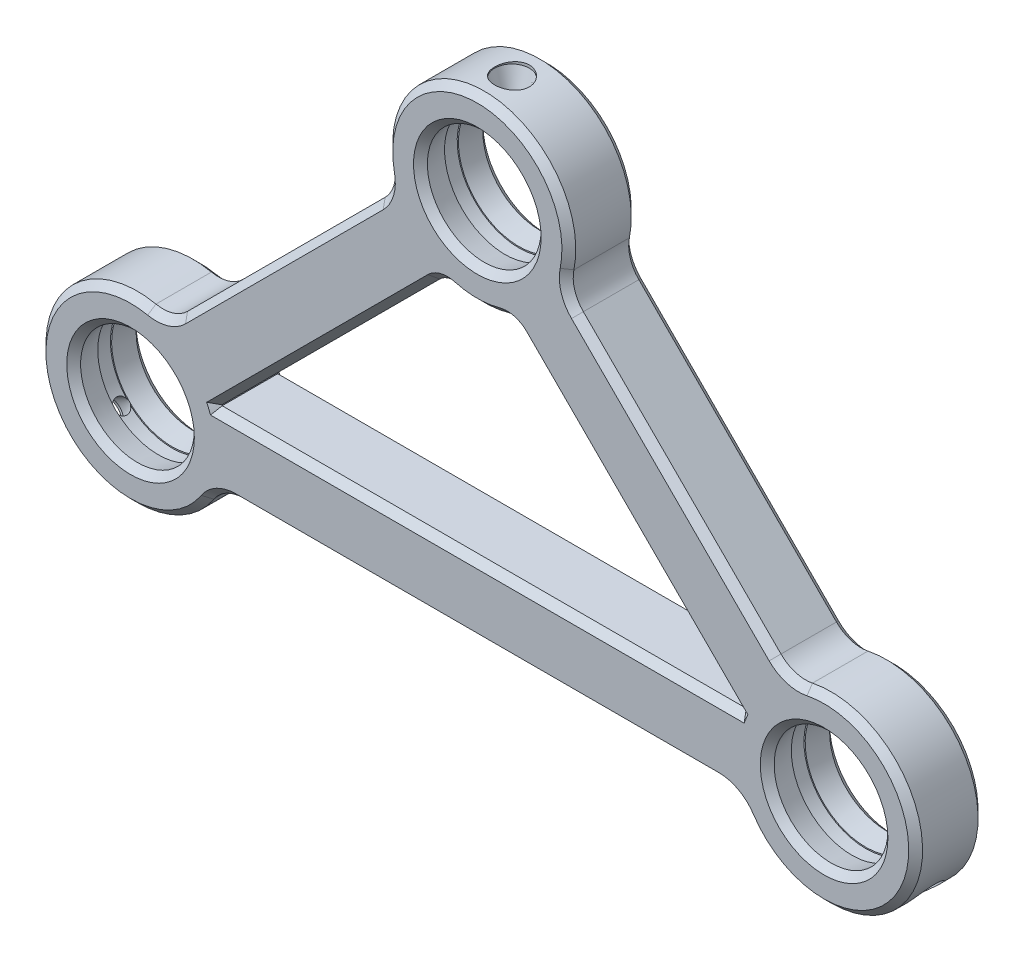
SolidWorks part; units mm, degrees
ref_plane "Front Plane" through (0, 0, 0) normal (0, 0, 1) x (1, 0, 0)
ref_plane "Top Plane" through (0, 0, 0) normal (0, 1, 0) x (1, 0, 0)
ref_plane "Right Plane" through (0, 0, 0) normal (1, 0, 0) x (0, 0, -1)
sketch "Sketch1" plane through (0, 0, 0) normal (0, 0, 1) x (1, 0, 0)
  line L0 (-26.538, 0) -> (73.462, 0) construction
  line L2 (-26.538, 0) -> (23.462, 50) construction
  line L3 (23.462, 50) -> (73.462, 0) construction
  line L4 (-14.3216, 5) -> (61.2456, 5)
  line L5 (-14.3216, -5) -> (61.2456, -5)
  line L6 (-21.4353, 12.1738) -> (11.2882, 44.8972)
  line L7 (18.3592, 37.8262) -> (-14.3642, 5.1028)
  line L8 (28.5647, 37.8262) -> (61.2882, 5.1028)
  line L9 (35.6358, 44.8972) -> (68.3592, 12.1738)
  circle A0 centre (23.462, 50) radius 8.2
  circle A1 centre (73.462, 0) radius 8.2
  circle A2 centre (-26.538, 0) radius 8.2
  circle A3 centre (-26.538, 0) radius 13.2
  circle A4 centre (23.462, 50) radius 13.2
  circle A5 centre (73.462, 0) radius 13.2
  dimension "D1" = 16.4
  dimension "D2" = 16.4
  dimension "D3" = 16.4
  dimension "D4" = 45
  dimension "D5" = 45
  dimension "D6" = 100
  dimension "D7" = 5
  dimension "D8" = 5
  dimension "D9" = 5
  dimension "D10" = 5
  dimension "D11" = 5
  dimension "D12" = 5
  dimension "D13" = 5
  dimension "D14" = 5
  dimension "D15" = 5
extrude "Boss-Extrude1" add sketch "Sketch1" along normal blind 8 contours A3 A2 | A4 L6 A3 L7 | A4 A0 | A5 L9 A4 L8 | A5 A1 | A5 L4 A3 L5 region at (23.462, 0, 0) region at (-13.9526, 2.4759, 0) region at (61.6117, 4.9085, 0) region at (-1.538, 25, 0) region at (48.462, 25, 0) region at (14.3922, 40.9302, 0)
sketch3d "3DSketch1" plane through (0, 0, 0) normal (0, 0, 1) x (1, 0, 0)
  dimension "D1" = 4
sketch "Sketch3" plane through (0, 0, 4) normal (0, 0, 1) x (1, 0, 0)
  circle A0 centre (-26.538, 0) radius 8.9053
  circle A1 centre (23.462, 50) radius 8.9053
  circle A2 centre (73.462, 0) radius 8.9053
  circle A3 centre (-26.538, 0) radius 8.2 construction
  circle A4 centre (23.462, 50) radius 8.2 construction
  circle A5 centre (73.462, 0) radius 8.2 construction
  dimension "D1" = 0.7053
  dimension "D2" = 0.7053
  dimension "D3" = 0.7053
extrude "Cut-Extrude1" cut sketch "Sketch3" against normal blind 1 and the other way blind 1 contours A1 | A0 | A2
sketch3d "3DSketch2" plane through (0, 0, 0) normal (0, 0, 1) x (1, 0, 0)
sketch3d "3DSketch3" plane through (0, 0, 0) normal (0, 0, 1) x (1, 0, 0)
  dimension "D1" = 26
sketch "Sketch4" plane through (0, 62.8, 0) normal (0, -1, 0) x (-1, 0, 0)
  line L0 (-41.8, -4) -> (41.8, -4) construction
  line L1 (-86.662, 0) -> (-86.662, -8) construction
  line L4 (-36.6606, -8) -> (-68.3592, -8)
  line L5 (-36.6606, -8) -> (-68.3592, -8)
  line L6 (-68.3592, -8) -> (-86.662, -8)
  line L7 (-68.3592, -8) -> (-86.662, -8)
  line L8 (-86.662, -8) -> (-86.662, 0)
  line L9 (-86.662, -8) -> (-86.662, 0)
  line L10 (-86.662, 0) -> (-68.3592, 0)
  line L11 (-86.662, 0) -> (-68.3592, 0)
  line L12 (-68.3592, 0) -> (-36.6606, 0)
  line L13 (-68.3592, 0) -> (-36.6606, 0)
  line L14 (-36.6606, 0) -> (-10.2633, 0)
  line L15 (-36.6606, 0) -> (-10.2633, 0)
  line L16 (-10.2633, 0) -> (21.4353, 0)
  line L17 (-10.2633, 0) -> (21.4353, 0)
  line L18 (21.4353, 0) -> (39.738, 0)
  line L19 (21.4353, 0) -> (39.738, 0)
  line L20 (39.738, 0) -> (39.738, -8)
  line L21 (39.738, 0) -> (39.738, -8)
  line L22 (39.738, -8) -> (21.4353, -8)
  line L23 (39.738, -8) -> (21.4353, -8)
  line L24 (21.4353, -8) -> (-10.2633, -8)
  line L25 (21.4353, -8) -> (-10.2633, -8)
  line L26 (-10.2633, -8) -> (-36.6606, -8)
  line L27 (-10.2633, -8) -> (-36.6606, -8)
  circle A0 centre (-23.462, -4) radius 2.5
  dimension "D1" = 5
  dimension "D2" = 63.2
  dimension "D3" = 126.4
extrude "Cut-Extrude2" cut sketch "Sketch4" along normal blind 6 draft 20 and the other way blind 10 contours A0
fillet "Fillet1" radius 3 2 edges at (18.3592, 37.8262, 4) (28.5647, 37.8262, 4)
fillet "Fillet2" radius 5 6 edges at (68.3592, 12.1738, 4) (35.6358, 44.8972, 4) (11.2882, 44.8972, 4) (-21.4353, 12.1738, 4) (-14.3216, -5, 4) (61.2456, -5, 4)
sketch3d "3DSketch4" plane through (0, 0, 0) normal (0, 0, 1) x (1, 0, 0)
sketch3d "3DSketch5" plane through (0, 0, 0) normal (0, 0, 1) x (1, 0, 0)
  dimension "D1" = 26
sketch "Sketch5" plane through (45.782, -45.782, 0) normal (-0.7071, 0.7071, 0) x (0, 0, 1)
  line L0 (8, -31.9652) -> (8, -7.7363) construction
  line L1 (8, 43.7455) -> (8, 60.1455) construction
  line L2 (8, 43.7455) -> (8, 60.1455)
  line L7 (8, 65.1455) -> (0, 65.1455) construction
  line L8 (8, 65.1455) -> (0, 65.1455)
  circle A0 centre (4, 51.9455) radius 2.5
  dimension "D1" = 5
  dimension "D2" = 4
  dimension "D3" = 8.2
  dimension "D4" = 16.4
extrude "Cut-Extrude3" cut sketch "Sketch5" along normal blind 6 draft 20 and the other way blind 10 contours A0 region at (82.513, -9.051, 4)
draft "Draft4" type of draft neutral plane draft angle 10 faces to draft 3 face at (-18.338, 0, 5) face at (31.662, 50, 5) face at (81.662, 0, 5) neutral plane through (0, 0, 8) neutral plane normal (0, 0, 1) reverse direction yes parameters "D1"=10
draft "Draft6" type of draft neutral plane draft angle 10 faces to draft 3 face at (-18.338, 0, 0) face at (81.662, 0, 0) face at (31.662, 50, 0) neutral plane through (0, 0, 0) neutral plane normal (0, 0, -1) reverse direction yes parameters "D1"=10
sketch3d "3DSketch6" plane through (0, 0, 0) normal (0, 0, 1) x (1, 0, 0)
sketch3d "3DSketch8" plane through (0, 0, 0) normal (0, 0, 1) x (1, 0, 0)
  dimension "D1" = 26
sketch "Sketch6" plane through (-22.32, -22.32, 0) normal (0.7071, 0.7071, 0) x (0, 0, -1)
  line L0 (-8, 31.9652) -> (-8, 5.5652) construction
  line L1 (0, 31.9652) -> (-8, 31.9652) construction
  line L2 (0, 31.9652) -> (-8, 31.9652)
  line L3 (0, 10.5652) -> (0, 26.9652) construction
  line L4 (0, 10.5652) -> (0, 26.9652)
  circle A0 centre (-4, 18.7652) radius 2.5
  dimension "D1" = 5
  dimension "D2" = 4
  dimension "D4" = 16.4
  dimension "D5" = 8.2
extrude "Cut-Extrude4" cut sketch "Sketch6" along normal blind 10 draft 20 and the other way blind 10 contours A0
sketch "Sketch7" plane through (0, 0, 8) normal (0, 0, 1) x (1, 0, 0)
  line L5 (17.0366, 36.5035) -> (-14.3642, 5.1028) construction
  line L10 (-14.3216, 5) -> (61.2456, 5) construction
  line L12 (29.8874, 36.5035) -> (61.2882, 5.1028) construction
  line L13 (17.0366, 36.5035) -> (-14.3642, 5.1028)
  line L20 (-14.3216, 5) -> (61.2456, 5)
  line L21 (66.2449, 14.2882) -> (37.7502, 42.7829)
  line L22 (9.1738, 42.7829) -> (-19.3209, 14.2882)
  line L23 (-11.3314, -5) -> (58.2554, -5)
  line L24 (66.2449, 14.2882) -> (37.7502, 42.7829)
  line L25 (9.1738, 42.7829) -> (-19.3209, 14.2882)
  line L26 (-11.3314, -5) -> (58.2554, -5)
  line L27 (29.8874, 36.5035) -> (61.2882, 5.1028)
  arc A36 (61.2882, 5.1028) -> (61.2456, 5) centre (73.462, 0) ccw construction
  arc A39 (-14.3216, 5) -> (-14.3642, 5.1028) centre (-26.538, 0) ccw construction
  arc A40 (19.955, 37.2744) -> (17.0366, 36.5035) centre (19.1579, 34.3822) ccw construction
  circle A70 centre (73.462, 0) radius 8.2 construction
  circle A71 centre (23.462, 50) radius 8.2 construction
  circle A72 centre (-26.538, 0) radius 8.2 construction
  circle A73 centre (73.462, 0) radius 8.2
  circle A74 centre (23.462, 50) radius 8.2
  circle A75 centre (-26.538, 0) radius 8.2
  arc A76 (29.8874, 36.5035) -> (26.969, 37.2744) centre (27.7661, 34.3822) ccw construction
  arc A77 (19.955, 37.2744) -> (26.969, 37.2744) centre (23.462, 50) ccw construction
  arc A78 (61.2882, 5.1028) -> (61.2456, 5) centre (73.462, 0) ccw
  arc A79 (36.3891, 47.3298) -> (37.7502, 42.7829) centre (41.2857, 46.3184) ccw
  arc A80 (36.3891, 47.3298) -> (10.5349, 47.3298) centre (23.462, 50) ccw
  arc A81 (9.1738, 42.7829) -> (10.5349, 47.3298) centre (5.6383, 46.3184) ccw
  arc A82 (-23.8678, 12.9271) -> (-19.3209, 14.2882) centre (-22.8564, 17.8237) ccw
  arc A83 (-23.8678, 12.9271) -> (-15.5091, -7.2527) centre (-26.538, 0) ccw
  arc A84 (-11.3314, -5) -> (-15.5091, -7.2527) centre (-11.3314, -10) ccw
  arc A85 (62.4331, -7.2527) -> (58.2554, -5) centre (58.2554, -10) ccw
  arc A86 (62.4331, -7.2527) -> (70.7918, 12.9271) centre (73.462, 0) ccw
  arc A87 (66.2449, 14.2882) -> (70.7918, 12.9271) centre (69.7804, 17.8237) ccw
  arc A88 (36.3891, 47.3298) -> (37.7502, 42.7829) centre (41.2857, 46.3184) ccw
  arc A89 (36.3891, 47.3298) -> (10.5349, 47.3298) centre (23.462, 50) ccw
  arc A90 (9.1738, 42.7829) -> (10.5349, 47.3298) centre (5.6383, 46.3184) ccw
  arc A91 (-23.8678, 12.9271) -> (-19.3209, 14.2882) centre (-22.8564, 17.8237) ccw
  arc A92 (-23.8678, 12.9271) -> (-15.5091, -7.2527) centre (-26.538, 0) ccw
  arc A93 (-11.3314, -5) -> (-15.5091, -7.2527) centre (-11.3314, -10) ccw
  arc A94 (62.4331, -7.2527) -> (58.2554, -5) centre (58.2554, -10) ccw
  arc A95 (62.4331, -7.2527) -> (70.7918, 12.9271) centre (73.462, 0) ccw
  arc A96 (66.2449, 14.2882) -> (70.7918, 12.9271) centre (69.7804, 17.8237) ccw
  arc A97 (-14.3216, 5) -> (-14.3642, 5.1028) centre (-26.538, 0) ccw
  arc A98 (19.955, 37.2744) -> (17.0366, 36.5035) centre (19.1579, 34.3822) ccw
  arc A99 (29.8874, 36.5035) -> (26.969, 37.2744) centre (27.7661, 34.3822) ccw
  arc A100 (19.955, 37.2744) -> (26.969, 37.2744) centre (23.462, 50) ccw
  dimension "D1" = 0
extrude "Boss-Extrude3" add sketch "Sketch7" along normal blind 1
sketch "Sketch11" plane through (0, 0, 0) normal (0, 0, -1) x (-1, 0, 0)
  line L13 (-61.2456, 5) -> (14.3216, 5)
  line L14 (-29.8874, 36.5035) -> (-61.2882, 5.1028)
  line L15 (14.3642, 5.1028) -> (-17.0366, 36.5035)
  line L16 (-61.2456, 5) -> (14.3216, 5)
  line L17 (-29.8874, 36.5035) -> (-61.2882, 5.1028)
  line L18 (14.3642, 5.1028) -> (-17.0366, 36.5035)
  line L19 (-37.7502, 42.7829) -> (-66.2449, 14.2882)
  line L20 (-58.2554, -5) -> (11.3314, -5)
  line L21 (19.3209, 14.2882) -> (-9.1738, 42.7829)
  line L22 (-37.7502, 42.7829) -> (-66.2449, 14.2882)
  line L23 (-58.2554, -5) -> (11.3314, -5)
  line L24 (19.3209, 14.2882) -> (-9.1738, 42.7829)
  circle A11 centre (-73.462, 0) radius 8.2
  circle A34 centre (-73.462, 0) radius 8.2
  circle A35 centre (-23.462, 50) radius 8.2
  circle A36 centre (-23.462, 50) radius 8.2
  circle A37 centre (26.538, 0) radius 8.2
  circle A38 centre (26.538, 0) radius 8.2
  arc A43 (14.3642, 5.1028) -> (14.3216, 5) centre (26.538, 0) ccw
  arc A44 (-61.2456, 5) -> (-61.2882, 5.1028) centre (-73.462, 0) ccw
  arc A45 (-26.969, 37.2744) -> (-29.8874, 36.5035) centre (-27.7661, 34.3822) ccw
  arc A46 (-26.969, 37.2744) -> (-19.955, 37.2744) centre (-23.462, 50) ccw
  arc A47 (-17.0366, 36.5035) -> (-19.955, 37.2744) centre (-19.1579, 34.3822) ccw
  arc A48 (14.3642, 5.1028) -> (14.3216, 5) centre (26.538, 0) ccw
  arc A49 (-61.2456, 5) -> (-61.2882, 5.1028) centre (-73.462, 0) ccw
  arc A50 (-26.969, 37.2744) -> (-29.8874, 36.5035) centre (-27.7661, 34.3822) ccw
  arc A51 (-26.969, 37.2744) -> (-19.955, 37.2744) centre (-23.462, 50) ccw
  arc A52 (-17.0366, 36.5035) -> (-19.955, 37.2744) centre (-19.1579, 34.3822) ccw
  arc A57 (-10.5349, 47.3298) -> (-36.3891, 47.3298) centre (-23.462, 50) ccw
  arc A58 (-37.7502, 42.7829) -> (-36.3891, 47.3298) centre (-41.2857, 46.3184) ccw
  arc A59 (-70.7918, 12.9271) -> (-66.2449, 14.2882) centre (-69.7804, 17.8237) ccw
  arc A60 (-70.7918, 12.9271) -> (-62.4331, -7.2527) centre (-73.462, 0) ccw
  arc A61 (-58.2554, -5) -> (-62.4331, -7.2527) centre (-58.2554, -10) ccw
  arc A62 (15.5091, -7.2527) -> (11.3314, -5) centre (11.3314, -10) ccw
  arc A63 (15.5091, -7.2527) -> (23.8678, 12.9271) centre (26.538, 0) ccw
  arc A64 (19.3209, 14.2882) -> (23.8678, 12.9271) centre (22.8564, 17.8237) ccw
  arc A65 (-10.5349, 47.3298) -> (-9.1738, 42.7829) centre (-5.6383, 46.3184) ccw
  arc A66 (-10.5349, 47.3298) -> (-36.3891, 47.3298) centre (-23.462, 50) ccw
  arc A67 (-37.7502, 42.7829) -> (-36.3891, 47.3298) centre (-41.2857, 46.3184) ccw
  arc A68 (-70.7918, 12.9271) -> (-66.2449, 14.2882) centre (-69.7804, 17.8237) ccw
  arc A69 (-70.7918, 12.9271) -> (-62.4331, -7.2527) centre (-73.462, 0) ccw
  arc A70 (-58.2554, -5) -> (-62.4331, -7.2527) centre (-58.2554, -10) ccw
  arc A71 (15.5091, -7.2527) -> (11.3314, -5) centre (11.3314, -10) ccw
  arc A72 (15.5091, -7.2527) -> (23.8678, 12.9271) centre (26.538, 0) ccw
  arc A73 (19.3209, 14.2882) -> (23.8678, 12.9271) centre (22.8564, 17.8237) ccw
  arc A74 (-10.5349, 47.3298) -> (-9.1738, 42.7829) centre (-5.6383, 46.3184) ccw
  dimension "D1" = 0
  dimension "D2" = 0
  dimension "D3" = 0
  dimension "D4" = 0
  dimension "D5" = 0
extrude "Boss-Extrude4" add sketch "Sketch11" along normal blind 1
chamfer "Chamfer1" distance 1 angle 45 46 edges at (-34.738, 0, -1) (65.262, 0, -1) (-5.0735, 28.5355, -1) (-21.4225, 13.0337, -1) (-38.7332, -5.0514, -1) (-13.7046, -5.5991, -1) (23.462, -5, -1) (60.6286, -5.5991, -1) (85.6572, -5.0514, -1) (68.3465, 13.0337, -1) (51.9975, 28.5355, -1) (36.4957, 44.8845, -1) (23.462, 63.2, -1) (10.4283, 44.8845, -1) (18.3918, 37.2827, -1) (23.462, 36.8, -1) (28.5322, 37.2827, -1) (45.5878, 20.8031, -1) (61.2668, 5.0514, -1) (23.462, 5, -1) (-14.3428, 5.0514, -1) (1.3362, 20.8031, -1) (15.262, 50, -1) (28.5322, 37.2827, 9) (23.462, 36.8, 9) (18.3918, 37.2827, 9) (1.3362, 20.8031, 9) (-14.3428, 5.0514, 9) (23.462, 5, 9) (61.2668, 5.0514, 9) (45.5878, 20.8031, 9) (-18.338, 0, 9) (81.662, 0, 9) (85.6572, -5.0514, 9) (60.6286, -5.5991, 9) (23.462, -5, 9) (-13.7046, -5.5991, 9) (-38.7332, -5.0514, 9) (-21.4225, 13.0337, 9) (-5.0735, 28.5355, 9) (10.4283, 44.8845, 9) (23.462, 63.2, 9) (36.4957, 44.8845, 9) (51.9975, 28.5355, 9) (68.3465, 13.0337, 9) (31.662, 50, 9)
equation "\"D2@Sketch1\"=\"D1@Sketch1\""
equation "\"D3@Sketch1\"=\"D1@Sketch1\""
equation "\"D5@Sketch1\"=\"D4@Sketch1\""
equation "\"D8@Sketch1\"=\"D7@Sketch1\""
equation "\"D9@Sketch1\"=\"D7@Sketch1\""
equation "\"D11@Sketch1\"=\"D10@Sketch1\""
equation "\"D12@Sketch1\"=\"D10@Sketch1\""
equation "\"D13@Sketch1\"=\"D10@Sketch1\""
equation "\"D14@Sketch1\"=\"D13@Sketch1\""
equation "\"D15@Sketch1\"=\"D14@Sketch1\""
equation "\"D2@Sketch3\"=\"D1@Sketch3\""
equation "\"D3@Sketch3\"=\"D1@Sketch3\""
equation "\"D2@Sketch4\"=\"D3@Sketch4\"/2"
equation "\"D3@Sketch5\"=\"D4@Sketch5\"/2"
equation "\"D2@Sketch5\"=\"D5@Sketch5\"/2"
equation "\"D2@Sketch6\"=\"D3@Sketch6\"/2"
equation "\"D5@Sketch6\"=\"D4@Sketch6\"/2"
equation "\"D1@Sketch3\"=4*tan(10)"
